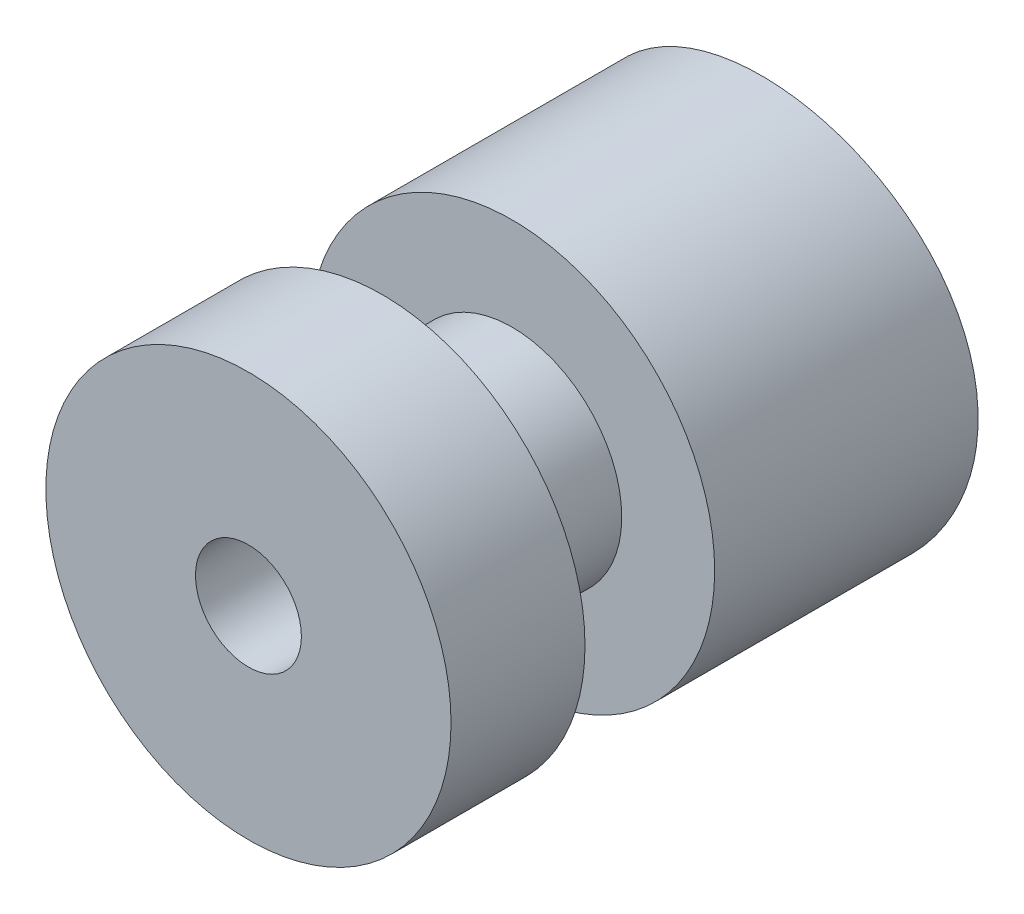
SolidWorks part; units mm, degrees
material "Nylon 6/10"
ref_plane "Front Plane" through (0, 0, 0) normal (0, 0, 1) x (1, 0, 0)
ref_plane "Top Plane" through (0, 0, 0) normal (0, 1, 0) x (1, 0, 0)
ref_plane "Right Plane" through (0, 0, 0) normal (1, 0, 0) x (0, 0, -1)
sketch "Sketch1" plane through (0, 0, 0) normal (0, 0, 1) x (1, 0, 0)
  circle A0 centre (0, 0) radius 9.525
  dimension "D1" = 19.05
extrude "Extrude1" add sketch "Sketch1" along normal blind 24.7828
ref_plane "Plane1" through (0, 0, 18.4836) normal (0, 0, 1) x (1, 0, 0)
sketch "Sketch2" plane through (0, 0, 18.4836) normal (0, 0, 1) x (1, 0, 0)
  circle A0 centre (0, 0) radius 5.1562
  dimension "D1" = 10.3124
extrude "Extrude2" cut sketch "Sketch2" against normal blind 6.096 flip side to cut
sketch "Sketch3" plane through (0, 0, 0) normal (0, 1, 0) x (1, 0, 0)
  arc A0 (9.525, 0) -> (-9.525, 0) centre (0, 69.1975) cw
  dimension "D1" = 69.85
extrude "Extrude3" cut sketch "Sketch3" against normal through all and the other way through all flip side to cut
hole_wizard "#10 Clearance Hole1" positions "Sketch5" profile "Sketch6" hole size "#10" standard "Ansi Inch" end condition through all
sketch "Sketch5" plane through (0, 0, 24.7828) normal (0, 0, 1) x (1, 0, 0)
  point P1 (0, 0)
sketch "Sketch6" plane through (0, 0, 24.7828) normal (1, 0, 0) x (0, -1, 0)
  line L0 (0, 0) -> (0, 24.7828)
  line L1 (0, 24.7828) -> (2.4892, 24.7828)
  line L2 (2.4892, 24.7828) -> (2.4892, 0)
  line L5 (2.4892, 0) -> (0, 0)
  line L11 (0, -6.35) -> (0, 107.95) construction
  dimension "Thru Hole Dia." = 4.9784
  dimension "Thru Hole Depth" = 24.7828
